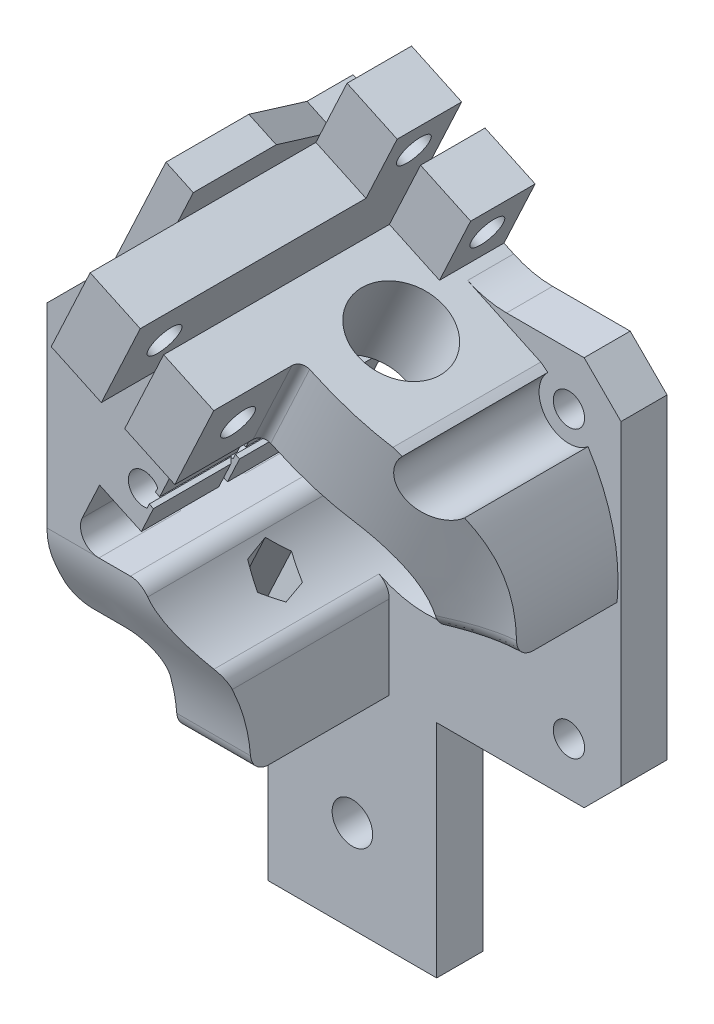
SolidWorks part; units mm, degrees
ref_plane "Plan de face" through (0, 0, 0) normal (0, 0, 1) x (1, 0, 0)
ref_plane "Plan de dessus" through (0, 0, 0) normal (0, 1, 0) x (1, 0, 0)
ref_plane "Plan de droite" through (0, 0, 0) normal (1, 0, 0) x (0, 0, -1)
sketch "Esquisse1" plane through (0, 0, 0) normal (0, 0, 1) x (1, 0, 0)
  line L0 (-21.15, 17.15) -> (-17.15, 21.15) construction
  line L1 (-17.15, 21.15) -> (17.15, 21.15) construction
  line L2 (17.15, 21.15) -> (21.15, 17.15) construction
  line L3 (21.15, 17.15) -> (21.15, -17.15) construction
  line L4 (-17.15, -21.15) -> (-21.15, -17.15) construction
  line L5 (-21.15, -17.15) -> (-21.15, 17.15) construction
  line L6 (-21.15, 17.15) -> (-17.15, 21.15)
  line L7 (-17.15, 21.15) -> (17.15, 21.15)
  line L8 (17.15, 21.15) -> (21.15, 17.15)
  line L9 (21.15, 17.15) -> (21.15, -17.15)
  line L10 (-17.15, -21.15) -> (-21.15, -17.15)
  line L11 (-21.15, -17.15) -> (-21.15, 17.15)
  line L12 (-17.15, -21.15) -> (-17.15, -45.15)
  line L13 (-17.15, -45.15) -> (1.15, -45.15)
  line L14 (17.15, -21.15) -> (1.15, -21.15)
  line L15 (21.15, -17.15) -> (17.15, -21.15)
  line L17 (1.15, -21.15) -> (1.15, -45.15)
  circle A0 centre (0, 0) radius 11.5 construction
  circle A1 centre (0, 0) radius 11.5
  dimension "D1" = 24
extrude "Boss.-Extru.1" add sketch "Esquisse1" along normal blind 5
hole_wizard "Dégagement M31" positions "Esquisse3" profile "Esquisse2" hole size "M3" standard "Din"
sketch "Esquisse3" plane through (0, 0, 5) normal (0, 0, 1) x (1, 0, 0)
  point P0 (15.5, 15.5)
  point P3 (15.5, -15.5)
  point P6 (-15.5, -15.5)
sketch "Esquisse2" plane through (15.5, 15.5, 5) normal (1, 0, 0) x (0, -1, 0)
  line L0 (0, 0) -> (0, 26)
  line L1 (0, 26) -> (1.7, 26)
  line L2 (1.7, 26) -> (1.7, 0)
  line L5 (1.7, 0) -> (0, 0)
  line L10 (0, 26) -> (-1.7, 26) construction
  line L11 (0, -6.35) -> (0, 107.95) construction
  dimension "Diamètre du perçage" = 3.4
  dimension "Profondeur du perçage" = 26
  dimension "Angle de pointe" = 180
hole_wizard "Dégagement M41" positions "Esquisse14" profile "Esquisse13" hole size "M4" standard "Din"
sketch "Esquisse14" plane through (0, 0, 5) normal (0, 0, 1) x (1, 0, 0)
  line L0 (-8, -35.15) -> (-8, -45.15) construction
  line L1 (-17.15, -45.15) -> (1.15, -45.15) construction
  point P0 (-8, -35.15)
  dimension "D1" = 10
sketch "Esquisse13" plane through (-8, -35.15, 5) normal (1, 0, 0) x (0, -1, 0)
  line L0 (0, 0) -> (0, 26)
  line L1 (0, 26) -> (2.2, 26)
  line L2 (2.2, 26) -> (2.2, 0)
  line L5 (2.2, 0) -> (0, 0)
  line L10 (0, 26) -> (-2.2, 26) construction
  line L11 (0, -6.35) -> (0, 107.95) construction
  dimension "Diamètre du perçage" = 4.4
  dimension "Profondeur du perçage" = 26
  dimension "Angle de pointe" = 180
sketch "Esquisse4" plane through (0, 0, 0) normal (0, 0, -1) x (-1, 0, 0)
  line L0 (-12.4361, 18.3876) -> (-8.2099, 9.3245)
  line L1 (-12.4361, 18.3876) -> (12.9238, 30.2131)
  line L2 (-8.2099, 9.3245) -> (17.15, 21.15)
  line L3 (12.9238, 30.2131) -> (17.15, 21.15)
  line L4 (-18.638, 48.2509) -> (23.6239, -42.3799) construction
  line L5 (21.15, -12) -> (15.5, -12)
  line L6 (21.15, 17.15) -> (21.15, -17.15) construction
  line L7 (12, -15.5) -> (12, -21.15)
  line L8 (12, -21.15) -> (4, -21.15)
  line L9 (4, -21.15) -> (4, -10.7819)
  line L10 (10.7819, -4) -> (21.15, -4)
  line L11 (21.15, -4) -> (21.15, -12)
  circle A1 centre (0, 0) radius 11.5 construction
  arc A2 (4, -10.7819) -> (10.7819, -4) centre (0, 0) ccw
  arc A3 (15.5, -12) -> (12, -15.5) centre (15.5, -15.5) ccw
  dimension "D7" = 8
  dimension "D8" = 3.5
  dimension "D1" = 7
  dimension "D2" = 10
  dimension "D3" = 3.5
  dimension "D4" = 3.5
  dimension "D6" = 8
extrude "Boss.-Extru.2" add sketch "Esquisse4" against normal blind 22
hole_wizard "Dégagement M51" positions "Esquisse25" profile "Esquisse24" hole size "M5" standard "Din"
sketch "Esquisse25" plane through (9.264, 19.8667, 0) normal (0.4226, 0.9063, 0) x (0.9063, -0.4226, 0)
  point P0 (-4.375, -13)
sketch "Esquisse24" plane through (5.2989, 21.7157, 13) normal (0, 0, 1) x (-0.9063, 0.4226, 0)
  line L0 (0, 0) -> (0, 4)
  line L1 (0, 4) -> (2.65, 4)
  line L2 (2.65, 4) -> (2.65, 0)
  line L5 (2.65, 0) -> (0, 0)
  line L10 (0, 4) -> (-2.65, 4) construction
  line L11 (0, -6.35) -> (0, 107.95) construction
  dimension "Diamètre du perçage" = 5.3
  dimension "Profondeur du perçage" = 4
  dimension "Angle de pointe" = 180
sketch "Esquisse5" plane through (9.264, 19.8667, 0) normal (0.4226, 0.9063, 0) x (0.9063, -0.4226, 0)
  circle A0 centre (-4.375, -13) radius 4.7
  dimension "D1" = 9.4
extrude "Enlèv. mat.-Extru.1" cut sketch "Esquisse5" against normal blind 15
sketch "Esquisse6" plane through (9.264, 19.8667, 0) normal (0.4226, 0.9063, 0) x (0.9063, -0.4226, 0)
  line L1 (-2.0224, -13.5878) -> (-2.6897, -11.2565)
  line L2 (-2.6897, -11.2565) -> (-5.0422, -10.6687)
  line L3 (-5.0422, -10.6687) -> (-6.7276, -12.4122)
  line L4 (-6.7276, -12.4122) -> (-6.0603, -14.7435)
  line L5 (-6.0603, -14.7435) -> (-3.7078, -15.3313)
  line L6 (-3.7078, -15.3313) -> (-2.0224, -13.5878)
  circle A0 centre (-4.375, -13) radius 2.1 construction
  dimension "D1" = 4.2
extrude "Enlèv. mat.-Extru.2" cut sketch "Esquisse6" against normal through all
sketch "Esquisse7" plane through (0, 0, 0) normal (0, 0, -1) x (-1, 0, 0)
  line L0 (-1.7449, 39.737) -> (-4.2826, 38.5537)
  line L1 (-1.7449, 39.737) -> (18.65, -4)
  line L2 (-4.2826, 38.5537) -> (6.8445, 14.6916)
  line L4 (12.9238, 30.2131) -> (-12.4361, 18.3876) construction
  line L5 (21.15, -4) -> (10.7819, -4) construction
  line L6 (0, 11.5) -> (6.8445, 14.6916)
  line L8 (0, 11.5) -> (10.7819, -4)
  line L9 (10.7819, -4) -> (18.65, -4)
  circle A0 centre (0, 0) radius 11.5 construction
  dimension "D1" = 2.8
  dimension "D2" = 2.5
extrude "Enlèv. mat.-Extru.3" cut sketch "Esquisse7" against normal through all
sketch "Esquisse8" plane through (0, 0, 0) normal (0, 0, 1) x (1, 0, 0)
  line L0 (-17.15, 21.15) -> (-21.15, 17.15)
  line L1 (-21.15, 17.15) -> (-21.15, -4)
  line L2 (-21.15, -4) -> (-18.65, -4)
  line L3 (-18.65, -4) -> (-15.4351, 2.8943)
  line L4 (-8.7491, 17.2326) -> (-17.15, 21.15)
  line L6 (-12.1387, 9.9635) -> (-7.6072, 7.8504)
  line L7 (-15.4351, 2.8943) -> (-10.9036, 0.7812)
  line L8 (-7.6072, 7.8504) -> (-10.9036, 0.7812)
  line L9 (0, 0) -> (-9.2554, 4.3158) construction
  line L10 (-12.1387, 9.9635) -> (-8.7491, 17.2326)
  dimension "D1" = 7.8
  dimension "D2" = 5
extrude "Boss.-Extru.3" add sketch "Esquisse8" along normal blind 25
hole_wizard "Dégagement M32" positions "Esquisse10" profile "Esquisse11" hole size "M3" standard "Din" end condition through all
sketch "Esquisse10" plane through (0, 0, 25) normal (0, 0, 1) x (1, 0, 0)
  line L0 (0, 0) -> (-10.6148, 4.9498) construction
  line L1 (-10.9036, 0.7812) -> (-7.6072, 7.8504) construction
  point P0 (-10.6148, 4.9498)
  dimension "D1" = 1.5
sketch "Esquisse11" plane through (-10.6148, 4.9498, 25) normal (1, 0, 0) x (0, -1, 0)
  line L0 (0, 0) -> (0, 25)
  line L1 (0, 25) -> (1.7, 25)
  line L2 (1.7, 25) -> (1.7, 0)
  line L5 (1.7, 0) -> (0, 0)
  line L11 (0, -6.35) -> (0, 107.95) construction
  dimension "Diamètre du perçage jusqu'au prochain" = 3.4
  dimension "Profondeur du perçage jusqu'au prochain" = 25
sketch "Esquisse12" plane through (0, 0, 25) normal (0, 0, 1) x (1, 0, 0)
  line L0 (-8.9173, 5.0409) -> (-8.6744, 5.5618)
  line L1 (-8.9173, 5.0409) -> (-9.3704, 5.2522)
  line L2 (-8.6744, 5.5618) -> (-9.1275, 5.7731)
  line L3 (-9.3704, 5.2522) -> (-9.1275, 5.7731)
  line L4 (-8.9173, 5.0409) -> (-7.6072, 7.8504) construction
  line L5 (-9.5935, 3.5908) -> (-9.8364, 3.0699)
  line L6 (-9.5935, 3.5908) -> (-10.0466, 3.8021)
  line L7 (-9.8364, 3.0699) -> (-10.2895, 3.2812)
  line L8 (-10.0466, 3.8021) -> (-10.2895, 3.2812)
  line L9 (-10.9036, 0.7812) -> (-9.5935, 3.5908) construction
  arc A0 (-8.9173, 5.0409) -> (-9.5935, 3.5908) centre (-10.6148, 4.9498) ccw construction
  dimension "D1" = 0.5
extrude "Boss.-Extru.5" add sketch "Esquisse12" against normal through all
ref_plane "Plan1" through (0, 0, 16.1) normal (0, 0, 1) x (1, 0, 0)
sketch "Esquisse15" plane through (0, 0, 16.1) normal (0, 0, 1) x (1, 0, 0)
  line L14 (-10.9036, 0.7812) -> (-9.5935, 3.5908)
  line L15 (-9.5935, 3.5908) -> (-10.0466, 3.8021)
  line L16 (-10.0466, 3.8021) -> (-10.2895, 3.2812)
  line L17 (-9.1275, 5.7731) -> (-9.3704, 5.2522)
  line L18 (-9.3704, 5.2522) -> (-8.9173, 5.0409)
  line L19 (-8.9173, 5.0409) -> (-7.6072, 7.8504)
  line L20 (-7.6072, 7.8504) -> (-12.1387, 9.9635)
  line L21 (-12.1387, 9.9635) -> (-8.7491, 17.2326)
  line L22 (-8.7491, 17.2326) -> (-17.15, 21.15)
  line L23 (-17.15, 21.15) -> (-21.15, 17.15)
  line L24 (-21.15, 17.15) -> (-21.15, -4)
  line L25 (-21.15, -4) -> (-18.65, -4)
  line L26 (-18.65, -4) -> (-15.4351, 2.8943)
  line L27 (-15.4351, 2.8943) -> (-10.9036, 0.7812)
  line L28 (-10.9036, 0.7812) -> (-9.5935, 3.5908)
  line L29 (-9.5935, 3.5908) -> (-10.0466, 3.8021)
  line L30 (-10.0466, 3.8021) -> (-10.2895, 3.2812)
  line L31 (-9.1275, 5.7731) -> (-9.3704, 5.2522)
  line L32 (-9.3704, 5.2522) -> (-8.9173, 5.0409)
  line L33 (-8.9173, 5.0409) -> (-7.6072, 7.8504)
  line L34 (-7.6072, 7.8504) -> (-12.1387, 9.9635)
  line L35 (-12.1387, 9.9635) -> (-8.7491, 17.2326)
  line L36 (-8.7491, 17.2326) -> (-17.15, 21.15)
  line L37 (-17.15, 21.15) -> (-21.15, 17.15)
  line L38 (-21.15, 17.15) -> (-21.15, -4)
  line L39 (-21.15, -4) -> (-18.65, -4)
  line L40 (-18.65, -4) -> (-15.4351, 2.8943)
  line L41 (-15.4351, 2.8943) -> (-10.9036, 0.7812)
  arc A1 (-9.1275, 5.7731) -> (-10.2895, 3.2812) centre (-10.6148, 4.9498) ccw
  arc A2 (-9.1275, 5.7731) -> (-10.2895, 3.2812) centre (-10.6148, 4.9498) ccw
  dimension "D1" = 0
extrude "Enlèv. mat.-Extru.4" cut sketch "Esquisse15" against normal blind 7
sketch "Esquisse16" plane through (0, 0, 22) normal (0, 0, 1) x (1, 0, 0)
  line L0 (-4.5229, 26.2957) -> (-8.7491, 17.2326)
  line L1 (-4.5229, 26.2957) -> (-9.9607, 28.8314)
  line L2 (-8.7491, 17.2326) -> (-14.1869, 19.7683)
  line L3 (-9.9607, 28.8314) -> (-14.1869, 19.7683)
  line L4 (-6.2114, 16.0493) -> (-1.9852, 25.1123)
  line L5 (-6.2114, 16.0493) -> (-0.7736, 13.5135)
  line L6 (-1.9852, 25.1123) -> (3.4526, 22.5766)
  line L7 (-0.7736, 13.5135) -> (3.4526, 22.5766)
  dimension "D1" = 6
  dimension "D2" = 6
extrude "Boss.-Extru.6" add sketch "Esquisse16" along normal blind 9.5
sketch "Esquisse17" plane through (9.264, 19.8667, 0) normal (0.4226, 0.9063, 0) x (0.9063, -0.4226, 0)
  line L0 (-15.2122, 0) -> (-21.2122, 0)
  line L1 (-15.2122, 0) -> (-15.2122, -7)
  line L2 (-21.2122, 0) -> (-21.2122, -7)
  line L3 (-15.2122, -7) -> (-21.2122, -7)
  line L5 (-12.4122, 0) -> (-6.4122, 0)
  line L6 (-12.4122, 0) -> (-12.4122, -7)
  line L7 (-6.4122, 0) -> (-6.4122, -7)
  line L8 (-12.4122, -7) -> (-6.4122, -7)
  line L9 (-12.4122, 0) -> (-3.0365, 0) construction
  dimension "D1" = 6
  dimension "D2" = 6
  dimension "D3" = 7
extrude "Boss.-Extru.7" add sketch "Esquisse17" along normal blind 8
hole_wizard "Dégagement M33" positions "Esquisse19" profile "Esquisse18" hole size "M3" standard "Din"
sketch "Esquisse19" plane through (-19.2248, 8.9646, 0) normal (-0.9063, 0.4226, 0) x (0, 0, 1)
  line L0 (26.75, 16.9205) -> (31.5, 16.9205) construction
  line L1 (31.5, 21.9205) -> (31.5, 11.9205) construction
  line L2 (26.75, 16.9205) -> (26.75, 21.9205) construction
  line L3 (31.5, 21.9205) -> (22, 21.9205) construction
  line L4 (3.5, 25.9205) -> (7, 25.9205) construction
  line L5 (7, 29.9205) -> (7, 21.9205) construction
  line L7 (3.5, 25.9205) -> (3.5, 29.9205) construction
  line L8 (0, 29.9205) -> (7, 29.9205) construction
  point P0 (26.75, 16.9205)
  point P2 (3.5, 25.9205)
sketch "Esquisse18" plane through (-12.0738, 24.2998, 26.75) normal (0, 0, 1) x (-0.4226, -0.9063, 0)
  line L0 (0, 0) -> (0, 16)
  line L1 (0, 16) -> (1.75, 16)
  line L2 (1.75, 16) -> (1.75, 0)
  line L5 (1.75, 0) -> (0, 0)
  line L10 (0, 16) -> (-1.75, 16) construction
  line L11 (0, -6.35) -> (0, 107.95) construction
  dimension "Diamètre du perçage" = 3.5
  dimension "Profondeur du perçage" = 16
  dimension "Angle de pointe" = 180
sketch "Esquisse20" plane through (0, 0, 22) normal (0, 0, 1) x (1, 0, 0)
  line L7 (-21.15, -4) -> (-21.15, -12)
  line L8 (-21.15, -12) -> (-15.5, -12)
  line L9 (-12, -15.5) -> (-12, -21.15)
  line L10 (-12, -21.15) -> (-4, -21.15)
  line L11 (-4, -21.15) -> (-4, -10.7819)
  line L12 (-10.7819, -4) -> (-18.65, -4)
  line L13 (-18.65, -4) -> (-21.15, -4)
  line L14 (-21.15, -4) -> (-21.15, -12)
  line L15 (-21.15, -12) -> (-15.5, -12)
  line L16 (-12, -15.5) -> (-12, -21.15)
  line L17 (-12, -21.15) -> (-4, -21.15)
  line L18 (-4, -21.15) -> (-4, -10.7819)
  line L19 (-10.7819, -4) -> (-18.65, -4)
  line L20 (-18.65, -4) -> (-21.15, -4)
  arc A2 (-12, -15.5) -> (-15.5, -12) centre (-15.5, -15.5) ccw
  arc A3 (-10.7819, -4) -> (-4, -10.7819) centre (0, 0) ccw
  arc A4 (-12, -15.5) -> (-15.5, -12) centre (-15.5, -15.5) ccw
  arc A5 (-10.7819, -4) -> (-4, -10.7819) centre (0, 0) ccw
  dimension "D1" = 0
extrude "Boss.-Extru.8" add sketch "Esquisse20" along normal up to surface (3 mm away)
fillet "Congé3" radius 2 2 edges at (-18.65, -4, 20.55) (-18.65, -4, 4.55)
sketch "Esquisse21" plane through (-21.15, 0, 0) normal (-1, 0, 0) x (0, 0, 1)
  line L1 (25, -4) -> (25, -21.15)
  line L2 (25, -21.15) -> (19.9796, -21.15)
  line L3 (25, -21.15) -> (5, -21.15) construction
  spline S0 degree 3 poles (25, -4) (24.9524, -9.204) (20.0063, -12.1779) (19.9796, -21.15) knots 0 0 0 0 1 1 1 1
extrude "Enlèv. mat.-Extru.6" cut sketch "Esquisse21" against normal up to surface (17.15 mm away) up to face at (-4, -15.966, 15)
fillet "Congé5" radius 10 1 edges at (6.512, 21.15, 2.5)
fillet "Congé7" radius 1 1 edges
fillet "Congé9" radius 2 1 edges at (0, 11.5, 2.5)
fillet "Congé10" radius 2 2 edges at (-4, -10.7819, 13.8359) (-10.7819, -4, 12.5)
chamfer "Chanfrein1" distance 2 angle 45 2 edges at (-8.2622, 6.4457, 0) (-10.2485, 2.186, 0) tangent propagation no
ref_plane "Plan2" through (0, 0, 9.45) normal (0, 0, 1) x (1, 0, 0)
sketch "Esquisse22" plane through (0, 0, 9.45) normal (0, 0, 1) x (1, 0, 0)
  line L0 (-12.1387, 9.9635) -> (-15.4351, 2.8943)
  line L1 (-15.6737, 9.2485) -> (-13.3175, 18.6484)
  line L2 (-15.2761, 8.6205) -> (-14.5204, 7.4273)
  line L3 (-14.5204, 7.4273) -> (-14.5204, 6.7294)
  line L4 (-17.4947, 20.4813) -> (-20.9169, 17.1821)
  line L5 (-20.9169, 17.1821) -> (-20.9169, -2.6968)
  line L6 (-18.4411, -1.7917) -> (-18.0738, -1.7917)
  line L7 (-20.6169, -2.3927) -> (-20.9169, -2.6968)
  line L8 (-17.4235, 20.1332) -> (-20.6169, 17.0546)
  line L9 (-20.6169, 16.305) -> (-20.6169, -2.3927)
  line L10 (-15.2761, 8.6205) -> (-12.6668, 18.3314)
  line L11 (-20.6169, -2.3927) -> (-17.7726, -2.3541) construction
  line L12 (-20.9169, -2.6968) -> (-17.7685, -2.6541) construction
  line L14 (-15.4351, 2.8943) -> (-10.9036, 0.7812)
  line L15 (-10.9036, 0.7812) -> (-9.5935, 3.5908)
  line L16 (-9.5935, 3.5908) -> (-10.0466, 3.8021)
  line L17 (-10.0466, 3.8021) -> (-10.2895, 3.2812)
  line L18 (-9.1275, 5.7731) -> (-9.3704, 5.2522)
  line L19 (-9.3704, 5.2522) -> (-8.9173, 5.0409)
  line L20 (-8.9173, 5.0409) -> (-7.6072, 7.8504)
  line L21 (-7.6072, 7.8504) -> (-12.1387, 9.9635)
  line L22 (-12.1387, 9.9635) -> (-8.7491, 17.2326)
  line L23 (-8.7491, 17.2326) -> (-17.15, 21.15)
  line L24 (-17.15, 21.15) -> (-21.15, 17.15)
  line L25 (-21.15, 17.15) -> (-21.15, -4)
  line L26 (-21.15, -4) -> (-15.5106, -4)
  line L27 (-17.3232, -1.1548) -> (-15.4351, 2.8943)
  line L28 (-15.4351, 2.8943) -> (-10.9036, 0.7812)
  line L29 (-10.9036, 0.7812) -> (-9.5935, 3.5908)
  line L30 (-9.5935, 3.5908) -> (-10.0466, 3.8021)
  line L31 (-10.0466, 3.8021) -> (-10.2895, 3.2812)
  line L32 (-9.1275, 5.7731) -> (-9.3704, 5.2522)
  line L33 (-9.3704, 5.2522) -> (-8.9173, 5.0409)
  line L34 (-8.9173, 5.0409) -> (-7.6072, 7.8504)
  line L35 (-7.6072, 7.8504) -> (-12.1387, 9.9635)
  line L36 (-15.4091, 8.1253) -> (-14.5204, 6.7294)
  line L37 (-18.0738, -1.7917) -> (-15.4091, 8.1253)
  line L38 (-18.4411, -1.7917) -> (-15.801, 8.7408)
  line L39 (-17.4947, 20.4813) -> (-17.4235, 20.1332)
  line L40 (-20.6169, 17.0546) -> (-20.6169, -2.3927) construction
  line L41 (-8.9113, 16.891) -> (-17.4235, 20.1332) construction
  line L42 (-13.3175, 18.6484) -> (-12.6668, 18.3314)
  line L44 (-20.6169, 16.305) -> (-15.801, 8.7408)
  line L45 (-20.6169, 17.0546) -> (-15.6737, 9.2485)
  line L57 (-8.8045, 17.1713) -> (-17.4947, 20.4813) construction
  arc A2 (-9.1275, 5.7731) -> (-10.2895, 3.2812) centre (-10.6148, 4.9498) ccw
  arc A3 (-17.3232, -1.1548) -> (-15.5106, -4) centre (-15.5106, -2) ccw
  arc A4 (-9.1275, 5.7731) -> (-10.2895, 3.2812) centre (-10.6148, 4.9498) ccw
  dimension "D1" = 0
extrude "Boss.-Extru.9" add sketch "Esquisse22" along normal blind 6.2 contours A4 L32 L33 L34 L35 L0 L28 L29 L30 L31 | L4 L5 L37 L38 L9 L8 region at (-9.9239, 8.7976, 9.45) region at (-14.2569, 13.8886, 9.45)
chamfer "Chanfrein2" distance 0.5 angle 45 4 edges at (-8.2622, 6.4457, 9.1) (-10.2485, 2.186, 9.1) (-10.2485, 2.186, 16.1) (-8.2622, 6.4457, 16.1)
sketch "Esquisse26" plane through (0, 0, 5) normal (0, 0, 1) x (1, 0, 0)
  line L0 (8.2099, 9.3245) -> (-6.2114, 16.0493) construction
  line L2 (13.7952, -0.0494) -> (20.7259, -0.0494)
  line L3 (12.4361, 18.3876) -> (8.2099, 9.3245)
  arc A0 (8.2099, 9.3245) -> (13.7952, -0.0494) centre (4.109, 0.5301) cw
  arc A1 (13.2123, 17.8006) -> (17.5729, 13.0041) centre (15.5, 15.5) ccw
  arc A2 (12.4361, 18.3876) -> (13.2123, 17.8006) centre (0.6641, 2.0124) cw
  arc A7 (17.5729, 13.0041) -> (20.7259, -0.0494) centre (0.6641, 2.0124) cw
extrude "Boss.-Extru.10" add sketch "Esquisse26" along normal up to surface (17 mm away) up to face at (6.2844, 15.7392, 22)
sketch "Esquisse27" plane through (5.0378, 10.8036, 0) normal (-0.4226, -0.9063, 0) x (0.9063, -0.4226, 0)
  line L0 (18.8049, 22) -> (18.8049, 5) construction
  line L1 (28.4108, 16) -> (9.199, 16) construction
  line L2 (1.3509, 22) -> (-12.1753, 22) construction
  line L3 (18.8049, 16) -> (18.8049, 22)
  line L4 (18.8049, 22) -> (-5.4122, 22)
  spline S0 degree 3 poles (-5.4122, 22) (9.1864, 22) (10.8, 16) (18.8049, 16) knots 0 0 0 0 1 1 1 1
  dimension "D1" = 6
extrude "Enlèv. mat.-Extru.7" cut sketch "Esquisse27" against normal through all and the other way blind 10
fillet "Congé11" radius 2 2 edges at (-8, -21.15, 19.9796)
sketch "Esquisse28" plane through (-22.1878, 10.3464, 0) normal (-0.9063, 0.4226, 0) x (0, 0, 1)
  line L0 (22, 21.9205) -> (22, 25.9205)
  line L1 (22, 25.9205) -> (13, 25.9205)
  line L2 (13, 25.9205) -> (5, 21.9205)
  line L3 (0, 21.9205) -> (7, 21.9205) construction
  line L4 (5, 21.9205) -> (22, 21.9205)
  dimension "D1" = 9
  dimension "D2" = 5
  dimension "D3" = 4
extrude "Boss.-Extru.11" add sketch "Esquisse28" against normal up to surface (3.2694 mm away) up to face at (-8.2703, 32.4566, 3.5)
fillet "Congé12" radius 2 1 edges at (-21.15, -12, 13.5388)
